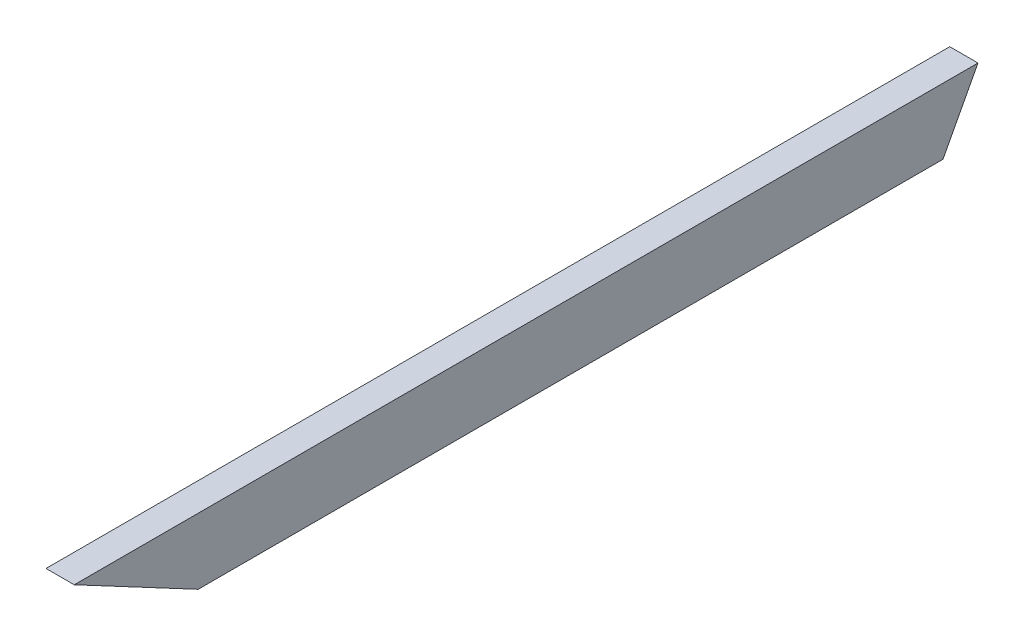
SolidWorks part; units mm, degrees
ref_plane "Front Plane" through (0, 0, 0) normal (0, 0, 1) x (1, 0, 0)
ref_plane "Top Plane" through (0, 0, 0) normal (0, 1, 0) x (1, 0, 0)
ref_plane "Right Plane" through (0, 0, 0) normal (1, 0, 0) x (0, 0, -1)
sketch "Sketch1" plane through (0, 0, 0) normal (0, 0, 1) x (1, 0, 0)
  line L1 (0, 0) -> (38.1, 0)
  line L2 (0, 0) -> (0, 88.9)
  line L3 (0, 88.9) -> (38.1, 88.9)
  line L4 (38.1, 0) -> (38.1, 88.9)
  dimension "D1" = 88.9
  dimension "D2" = 38.1
extrude "Boss-Extrude1" add sketch "Sketch1" along normal blind 1219.2
sketch "Sketch2" plane through (38.1, 0, 0) normal (1, 0, 0) x (0, 0, -1)
  line L0 (-1219.2, 88.9) -> (-1052.0034, 0)
  line L1 (-1219.2, 0) -> (0, 0) construction
  line L2 (-1052.0034, 0) -> (-1219.2, 0)
  line L3 (-1219.2, 0) -> (-1219.2, 88.9)
  dimension "D1" = 62
extrude "Cut-Extrude1" cut sketch "Sketch2" against normal through all
sketch "Sketch3" plane through (38.1, 0, 0) normal (1, 0, 0) x (0, 0, -1)
  line L2 (-1052.0034, 0) -> (0, 0) construction
  line L5 (0, 88.9) -> (-47.269, 0)
  line L7 (0, 88.9) -> (0, 0)
  line L8 (-47.269, 0) -> (0, 0)
  dimension "D1" = 28
extrude "Cut-Extrude2" cut sketch "Sketch3" against normal through all
